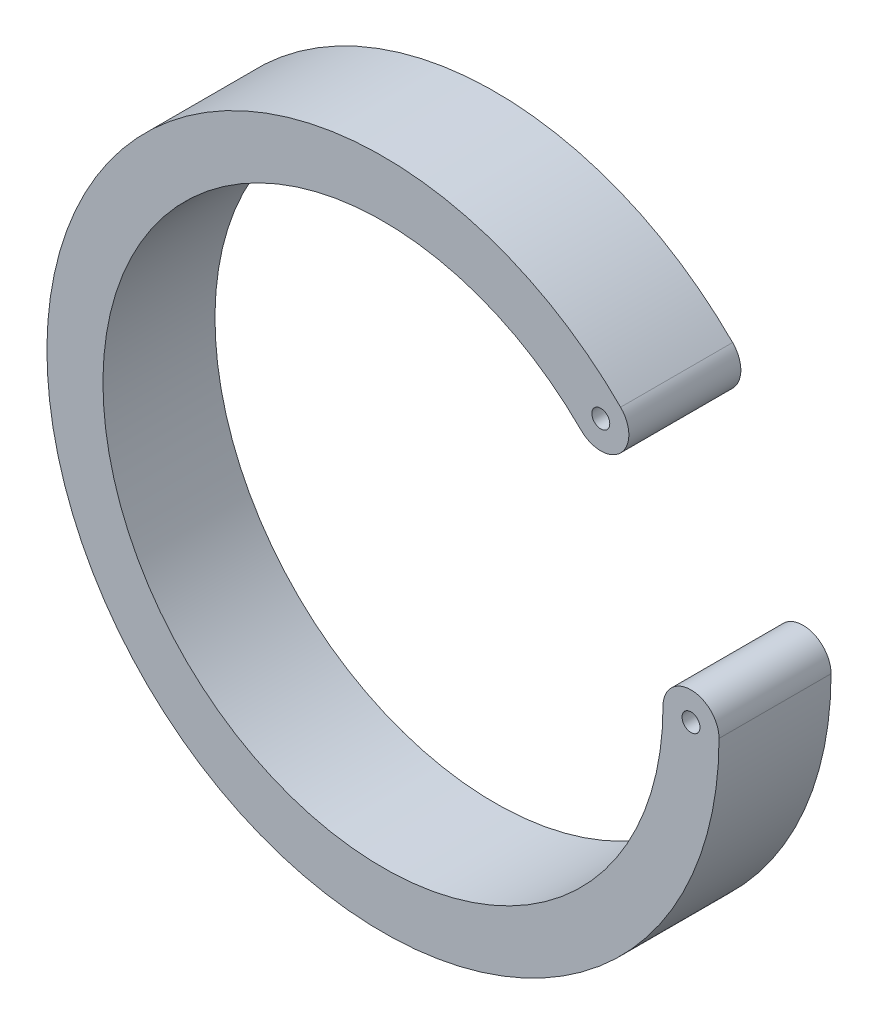
SolidWorks part; units mm, degrees
ref_plane "Front Plane" through (0, 0, 0) normal (0, 0, 1) x (1, 0, 0)
ref_plane "Top Plane" through (0, 0, 0) normal (0, 1, 0) x (1, 0, 0)
ref_plane "Right Plane" through (0, 0, 0) normal (1, 0, 0) x (0, 0, -1)
sketch "Sketch1" plane through (0, 0, 0) normal (0, 0, 1) x (1, 0, 0)
  line L0 (22.4506, 22.4506) -> (26.9408, 26.9408) construction
  line L1 (31.75, 0) -> (38.1, 0) construction
  line L2 (0, 0) -> (31.75, 0) construction
  arc A0 (22.4506, 22.4506) -> (31.75, 0) centre (0, 0) ccw
  arc A1 (26.9408, 26.9408) -> (38.1, 0) centre (0, 0) ccw
  arc A2 (31.75, 0) -> (38.1, 0) centre (34.925, 0) cw
  arc A3 (26.9408, 26.9408) -> (22.4506, 22.4506) centre (24.6957, 24.6957) cw
  circle A4 centre (34.925, 0) radius 1.016
  circle A5 centre (24.6957, 24.6957) radius 1.016
  dimension "D1" = 31.75
  dimension "D2" = 2.032
  dimension "D3" = 38.1
  dimension "D4" = 45
extrude "Boss-Extrude1" add sketch "Sketch1" along normal blind 12.7 contours A3 A1 A2 A0 A5 A4 region at (-30.3288, -12.5626, 0)
equation "\"D3@Sketch1\"=\"D1@Sketch1\"+.25"
